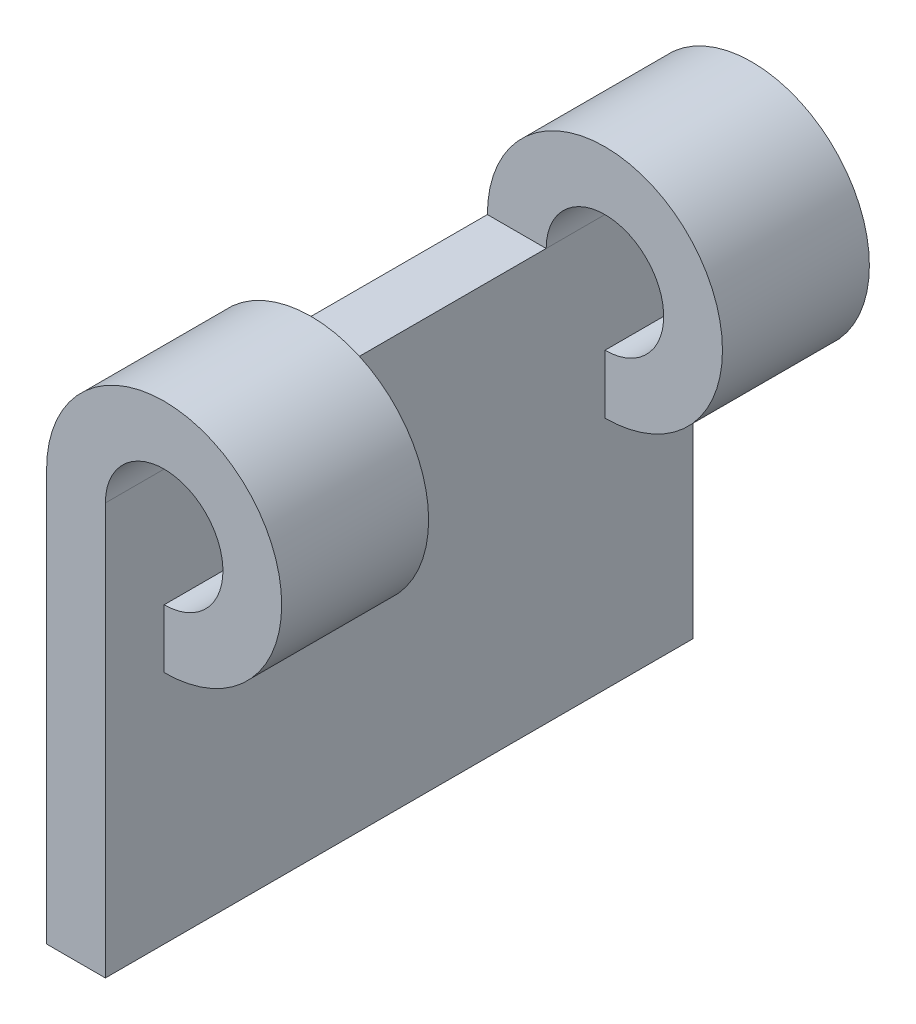
SolidWorks part; units mm, degrees
ref_plane "Front Plane" through (0, 0, 0) normal (0, 0, 1) x (1, 0, 0)
ref_plane "Top Plane" through (0, 0, 0) normal (0, 1, 0) x (1, 0, 0)
ref_plane "Right Plane" through (0, 0, 0) normal (1, 0, 0) x (0, 0, -1)
sketch "Sketch2" plane through (0, 0, 0) normal (0, 0, 1) x (1, 0, 0)
  line L0 (0, 0) -> (0, 14)
  line L1 (0, 14) -> (2, 14)
  line L2 (2, 14) -> (2, 0)
  line L3 (2, 0) -> (0, 0)
  line L4 (2, 14) -> (2, 10) construction
  line L5 (0, 14) -> (4, 14) construction
  line L6 (4, 18) -> (4, 10) construction
  line L7 (4, 14) -> (8, 14) construction
  line L8 (4, 12) -> (4, 10)
  arc A0 (2, 10.5359) -> (0, 14) centre (4, 14) ccw
  circle A1 centre (4, 14) radius 2
  dimension "D3" = 8
  dimension "D4" = 4
  dimension "D1" = 14
  dimension "D2" = 2
extrude "Boss-Extrude1" add sketch "Sketch2" along normal blind 20 contours L3 L2 L1 L0 region at (1, 7, 0)
extrude "Boss-Extrude2" add sketch "Sketch2<5>" along normal blind 5 separate body contours A1 L8 A0 L1 region at (6.7484, 16.7484, 0)
sketch "Sketch2<5>" plane through (0, 0, 0) normal (0, 0, 1) x (1, 0, 0) same geometry as "Sketch2"
ref_plane "Plane1" through (0, 0, 10) normal (0, 0, 1) x (1, 0, 0)
extrude "Boss-Extrude3" add sketch "Sketch2<6>" along normal blind 5 from offset 15 contours A1 L8 A0 L1 region at (6.7484, 16.7484, 0)
sketch "Sketch2<6>" plane through (0, 0, 0) normal (0, 0, 1) x (1, 0, 0) same geometry as "Sketch2"
